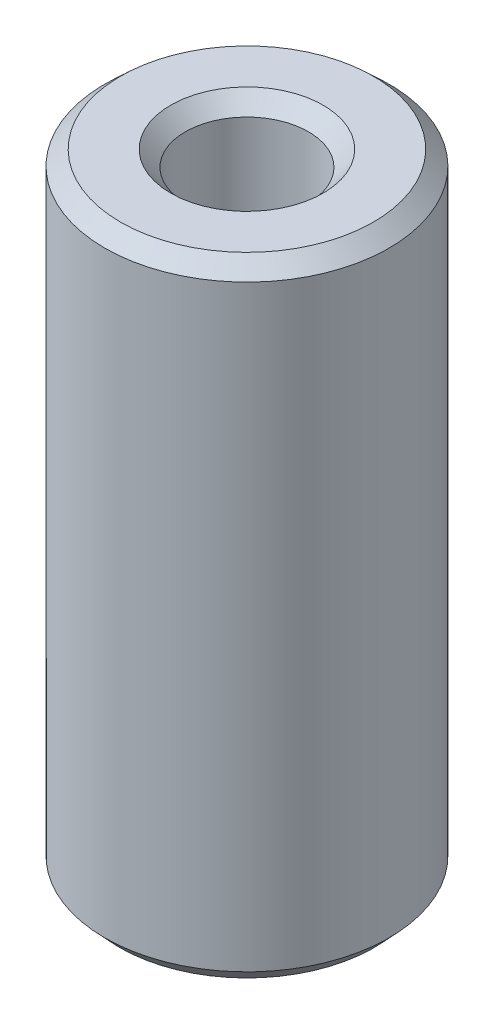
SolidWorks part; units mm, degrees
ref_plane "Front Plane" through (0, 0, 0) normal (0, 0, 1) x (1, 0, 0)
ref_plane "Top Plane" through (0, 0, 0) normal (0, 1, 0) x (1, 0, 0)
ref_plane "Right Plane" through (0, 0, 0) normal (1, 0, 0) x (0, 0, -1)
sketch "Sketch1" plane through (0, 0, 0) normal (0, 1, 0) x (1, 0, 0)
  circle A0 centre (0, 0) radius 32.5
  dimension "SLEEVE_OD" = 65
extrude "Boss-Extrude1" add sketch "Sketch1" along normal blind 143.563
sketch "Sketch2" plane through (0, 0, 0) normal (0, 1, 0) x (1, 0, 0)
  circle A0 centre (0, 0) radius 14.0769
  dimension "BORE_D" = 28.1538
extrude "Cut-Extrude1" cut sketch "Sketch2" along normal through all
chamfer "Chamfer1" distance 3.3584 angle 46.882 4 edges at (0, 143.563, 14.0769) (0, 0, 14.0769) (0, 0, 32.5) (0, 143.563, 32.5) first distance on face at (0, 143.563, 14.0769) first distance on face at (0, 0, 14.0769) first distance on face at (0, 143.563, 32.5)
